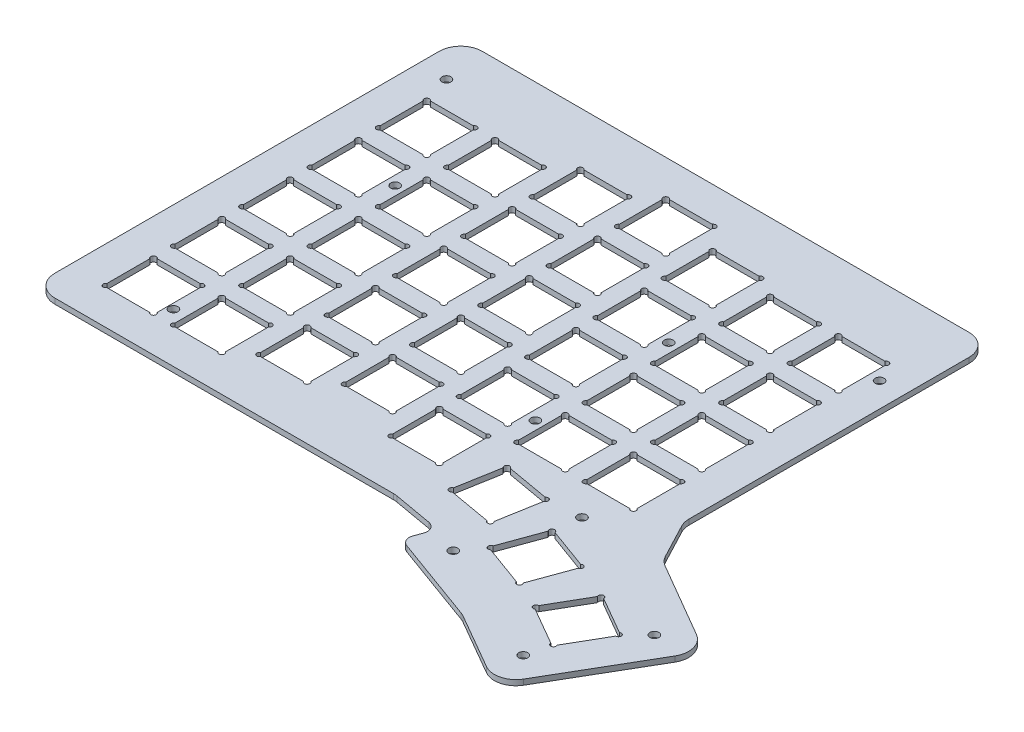
SolidWorks part; units mm, degrees
ref_plane "Front Plane" through (0, 0, 0) normal (0, 0, 1) x (1, 0, 0)
ref_plane "Top Plane" through (0, 0, 0) normal (0, 1, 0) x (1, 0, 0)
ref_plane "Right Plane" through (0, 0, 0) normal (1, 0, 0) x (0, 0, -1)
sketch "Sketch1" plane through (0, 0, 0) normal (0, 1, 0) x (1, 0, 0)
  line L0 (-117.355, 131.5231) -> (30.445, 131.523)
  line L3 (36.9567, 33.5861) -> (64.5736, 17.5122)
  line L4 (64.5736, 17.5122) -> (43.0375, -19.4893)
  line L5 (43.0375, -19.4893) -> (21.8815, -7.2748)
  line L6 (21.8815, -7.2748) -> (-4.8241, 2.4452)
  line L7 (-4.8241, 2.4452) -> (-2.1415, 9.8154)
  line L8 (-2.1415, 9.8154) -> (-16.3627, 12.323)
  line L9 (-16.3627, 12.323) -> (-117.355, 12.3231)
  line L10 (-117.355, 12.3231) -> (-117.355, 131.5231)
  line L12 (36.9567, 33.5861) -> (30.445, 45.9585)
  line L13 (30.445, 45.9585) -> (30.445, 131.523)
  line L22 (-114.355, 124.3231) -> (-114.355, 19.5231) construction
  line L24 (24.245, 128.523) -> (-110.155, 128.5231) construction
  line L26 (27.445, 40.923) -> (27.445, 125.323) construction
  line L27 (31.445, 33.323) -> (27.445, 40.923) construction
  line L30 (57.045, 18.423) -> (31.445, 33.323) construction
  line L31 (43.961, -12.1898) -> (58.3385, 12.7128) construction
  line L32 (23.0806, -4.503) -> (38.1322, -13.1931) construction
  line L33 (2.645, 2.923) -> (23.0806, -4.503) construction
  line L34 (-16.3823, 15.323) -> (0.7426, 12.3612) construction
  line L35 (1.4596, 10.95) -> (0.545, 8.423) construction
  dimension "D1" = 119.2
  dimension "D7" = 20
  dimension "D5" = 10
  dimension "D8" = 30
  dimension "D3" = 3
  dimension "D2" = 3
  dimension "D4" = 3
  dimension "D6" = 5
  dimension "D9" = 3
  dimension "D10" = 3
  dimension "D11" = 3
  dimension "D12" = 3
  dimension "D13" = 3
  dimension "D14" = 3
extrude "Boss-Extrude1" add sketch "Sketch1" against normal blind 1.5
sketch "Sketch2" plane through (0, 0, 0) normal (0, 1, 0) x (1, 0, 0)
  line L0 (-50.467, 121.823) -> (-36.467, 107.823) construction
  line L1 (-50.467, 121.823) -> (-36.467, 121.823)
  line L2 (-50.467, 121.823) -> (-50.467, 107.823)
  line L3 (-50.467, 107.823) -> (-36.467, 107.823)
  line L4 (-36.467, 121.823) -> (-36.467, 107.823)
  line L5 (-36.467, 121.823) -> (-50.467, 107.823) construction
  line L6 (30.445, 131.523) -> (-117.355, 131.5231) construction
  line L7 (-117.355, 131.5231) -> (-117.355, 12.3231) construction
  circle A0 centre (-50.1135, 121.4695) radius 0.75
  circle A1 centre (-36.8206, 121.4695) radius 0.75
  circle A2 centre (-36.8206, 108.1766) radius 0.75
  circle A3 centre (-50.1135, 108.1766) radius 0.75
  dimension "D5" = 1.5
  dimension "D1" = 14
  dimension "D3" = 9.7
  dimension "D2" = 66.888
  dimension "D4" = 0.5
extrude "Cut-Extrude1" cut sketch "Sketch2" against normal blind 10 contours L2 L3 L4 L1 | A0 | A3 | A2 | A1
sketch "Sketch3" plane through (0, 0, 0) normal (0, 1, 0) x (1, 0, 0)
  line L0 (-37.482, 121.823) -> (-49.452, 121.823) construction
  line L1 (-69.517, 117.0605) -> (-55.517, 117.0605)
  line L2 (-69.517, 117.0605) -> (-69.517, 103.0605)
  line L3 (-69.517, 103.0605) -> (-55.517, 103.0605)
  line L4 (-55.517, 117.0605) -> (-55.517, 103.0605)
  line L5 (-50.467, 114.823) -> (-36.467, 114.823) construction
  line L6 (-50.467, 120.8081) -> (-50.467, 108.838) construction
  line L7 (-36.467, 120.8081) -> (-36.467, 108.838) construction
  line L9 (-69.517, 117.0605) -> (-55.517, 103.0605) construction
  line L10 (-55.517, 117.0605) -> (-69.517, 103.0605) construction
  circle A0 centre (-69.1635, 116.707) radius 0.75
  circle A1 centre (-55.8706, 116.707) radius 0.75
  circle A2 centre (-55.8706, 103.4141) radius 0.75
  circle A3 centre (-69.1635, 103.4141) radius 0.75
  point P6 (-43.467, 121.823)
  point P7 (-62.517, 117.0605)
  dimension "D4" = 1.5
  dimension "D1" = 19.05
  dimension "D2" = 4.7625
  dimension "D3" = 0.5
sketch "Sketch4" plane through (0, 0, 0) normal (0, 1, 0) x (1, 0, 0)
  line L0 (-37.482, 121.823) -> (-49.452, 121.823) construction
  line L1 (-88.567, 112.298) -> (-74.567, 112.298)
  line L2 (-88.567, 112.298) -> (-88.567, 98.298)
  line L3 (-88.567, 98.298) -> (-74.567, 98.298)
  line L4 (-74.567, 112.298) -> (-74.567, 98.298)
  line L5 (-55.517, 117.0605) -> (-55.517, 103.0605) construction
  line L6 (-50.467, 114.823) -> (-36.467, 114.823) construction
  line L7 (-50.467, 120.8081) -> (-50.467, 108.838) construction
  line L8 (-36.467, 120.8081) -> (-36.467, 108.838) construction
  line L9 (-88.567, 112.298) -> (-74.567, 98.298) construction
  line L10 (-74.567, 112.298) -> (-88.567, 98.298) construction
  circle A0 centre (-88.2135, 111.9445) radius 0.75
  circle A1 centre (-74.9206, 111.9445) radius 0.75
  circle A2 centre (-74.9206, 98.6516) radius 0.75
  circle A3 centre (-88.2135, 98.6516) radius 0.75
  dimension "D4" = 0.5
  dimension "D3" = 1.5
  dimension "D1" = 9.525
  dimension "D2" = 19.05
sketch "Sketch5" plane through (0, 0, 0) normal (0, 1, 0) x (1, 0, 0)
  line L0 (-37.482, 121.823) -> (-49.452, 121.823) construction
  line L1 (-107.617, 112.298) -> (-93.617, 112.298)
  line L2 (-107.617, 112.298) -> (-107.617, 98.298)
  line L3 (-107.617, 98.298) -> (-93.617, 98.298)
  line L4 (-93.617, 112.298) -> (-93.617, 98.298)
  line L5 (-74.567, 112.298) -> (-74.567, 98.298) construction
  line L6 (-50.467, 114.823) -> (-36.467, 114.823) construction
  line L7 (-50.467, 120.8081) -> (-50.467, 108.838) construction
  line L8 (-36.467, 120.8081) -> (-36.467, 108.838) construction
  line L10 (-107.617, 112.298) -> (-93.617, 98.298) construction
  line L11 (-93.617, 112.298) -> (-107.617, 98.298) construction
  circle A0 centre (-107.2635, 111.9445) radius 0.75
  circle A1 centre (-93.9706, 111.9445) radius 0.75
  circle A2 centre (-93.9706, 98.6516) radius 0.75
  circle A3 centre (-107.2635, 98.6516) radius 0.75
  dimension "D4" = 1.5
  dimension "D1" = 19.05
  dimension "D3" = 0.5
  dimension "D2" = 9.525
sketch "Sketch6" plane through (0, 0, 0) normal (0, 1, 0) x (1, 0, 0)
  line L0 (-37.482, 121.823) -> (-49.452, 121.823) construction
  line L1 (-31.417, 115.823) -> (-17.417, 115.823)
  line L2 (-31.417, 115.823) -> (-31.417, 101.823)
  line L3 (-31.417, 101.823) -> (-17.417, 101.823)
  line L4 (-17.417, 115.823) -> (-17.417, 101.823)
  line L5 (-50.467, 120.8081) -> (-50.467, 108.838) construction
  line L6 (-31.417, 115.823) -> (-17.417, 101.823) construction
  line L7 (-17.417, 115.823) -> (-31.417, 101.823) construction
  line L8 (-50.467, 114.823) -> (-36.467, 114.823) construction
  line L9 (-50.467, 120.8081) -> (-50.467, 108.838) construction
  line L10 (-36.467, 120.8081) -> (-36.467, 108.838) construction
  circle A0 centre (-17.7706, 115.4695) radius 0.75
  circle A1 centre (-31.0635, 115.4695) radius 0.75
  circle A2 centre (-31.0635, 102.1766) radius 0.75
  circle A3 centre (-17.7706, 102.1766) radius 0.75
  dimension "D4" = 1.5
  dimension "D3" = 0.5
  dimension "D2" = 19.05
  dimension "D1" = 6
sketch "Sketch7" plane through (0, 0, 0) normal (0, 1, 0) x (1, 0, 0)
  line L0 (-37.482, 121.823) -> (-49.452, 121.823) construction
  line L1 (-12.367, 112.823) -> (1.633, 112.823)
  line L2 (-12.367, 112.823) -> (-12.367, 98.823)
  line L3 (-12.367, 98.823) -> (1.633, 98.823)
  line L4 (1.633, 112.823) -> (1.633, 98.823)
  line L5 (-31.417, 115.823) -> (-31.417, 101.823) construction
  line L6 (-12.367, 112.823) -> (1.633, 98.823) construction
  line L7 (1.633, 112.823) -> (-12.367, 98.823) construction
  line L8 (-36.467, 114.823) -> (-50.467, 114.823) construction
  line L9 (-36.467, 120.8081) -> (-36.467, 108.838) construction
  line L10 (-50.467, 120.8081) -> (-50.467, 108.838) construction
  circle A0 centre (-12.0135, 112.4695) radius 0.75
  circle A1 centre (1.2794, 112.4695) radius 0.75
  circle A2 centre (1.2794, 99.1766) radius 0.75
  circle A3 centre (-12.0135, 99.1766) radius 0.75
  dimension "D4" = 1.5
  dimension "D3" = 0.5
  dimension "D2" = 19.05
  dimension "D1" = 9
sketch "Sketch8" plane through (0, 0, 0) normal (0, 1, 0) x (1, 0, 0)
  line L0 (-37.482, 121.823) -> (-49.452, 121.823) construction
  line L1 (6.683, 112.823) -> (20.683, 112.823)
  line L2 (6.683, 112.823) -> (6.683, 98.823)
  line L3 (6.683, 98.823) -> (20.683, 98.823)
  line L4 (20.683, 112.823) -> (20.683, 98.823)
  line L5 (-12.367, 112.823) -> (-12.367, 98.823) construction
  line L6 (6.683, 112.823) -> (20.683, 98.823) construction
  line L7 (20.683, 112.823) -> (6.683, 98.823) construction
  line L8 (-50.467, 114.823) -> (-36.467, 114.823) construction
  line L9 (-50.467, 120.8081) -> (-50.467, 108.838) construction
  line L10 (-36.467, 120.8081) -> (-36.467, 108.838) construction
  circle A0 centre (7.0365, 112.4695) radius 0.75
  circle A1 centre (20.3294, 112.4695) radius 0.75
  circle A2 centre (20.3294, 99.1766) radius 0.75
  circle A3 centre (7.0365, 99.1766) radius 0.75
  dimension "D4" = 1.5
  dimension "D1" = 19.05
  dimension "D3" = 0.5
  dimension "D2" = 9
extrude "Cut-Extrude2" cut sketch "Sketch3" against normal blind 10 contours L1 L4 L3 L2 | A0 | A1 | A2 | A3
extrude "Cut-Extrude3" cut sketch "Sketch4" against normal blind 10 contours L1 L4 L3 L2 | A0 | A1 | A2 | A3
extrude "Cut-Extrude4" cut sketch "Sketch5" against normal blind 10 contours A0 | L1 L4 L3 L2 | A1 | A2 | A3
extrude "Cut-Extrude5" cut sketch "Sketch6" against normal blind 10 contours L1 L4 L3 L2 | A1 | A0 | A3 | A2
extrude "Cut-Extrude6" cut sketch "Sketch7" against normal blind 10 contours A0 | L1 L4 L3 L2 | A1 | A3 | A2
extrude "Cut-Extrude7" cut sketch "Sketch8" against normal blind 10 contours L1 L4 L3 L2 | A1 | A0 | A3 | A2
pattern_linear "LPattern1" count 5 spacing 19.05 along (0, 0, 1) of "Cut-Extrude5", "Cut-Extrude1", "Cut-Extrude2", "Cut-Extrude3", "Cut-Extrude4"
pattern_linear "LPattern2" count 4 spacing 19.05 along (0, 0, 1) of "Cut-Extrude7", "Cut-Extrude6"
sketch "Sketch10" plane through (0, 0, 0) normal (0, 1, 0) x (1, 0, 0)
  line L0 (-33.417, 41.623) -> (-15.417, 41.623) construction
  line L1 (-15.417, 41.623) -> (-15.417, 23.623) construction
  line L2 (-15.417, 23.623) -> (-33.417, 23.623) construction
  line L3 (-33.417, 23.623) -> (-33.417, 41.623) construction
  line L4 (-14.367, 57.673) -> (3.633, 57.673) construction
  line L5 (3.633, 57.673) -> (3.633, 39.673) construction
  line L6 (3.633, 39.673) -> (-14.367, 39.673) construction
  line L7 (-14.367, 39.673) -> (-14.367, 57.673) construction
  line L8 (-30.402, 39.623) -> (-18.432, 39.623) construction
  line L9 (-31.417, 38.6081) -> (-31.417, 26.638) construction
  line L10 (-11.352, 55.673) -> (0.618, 55.673) construction
  line L11 (-12.367, 54.6581) -> (-12.367, 42.688) construction
  line L12 (-7.669, 34.8561) -> (6.1183, 32.4251)
  line L13 (-7.669, 34.8561) -> (-10.1001, 21.0688)
  line L14 (6.1183, 32.4251) -> (3.6872, 18.6378)
  line L15 (-10.1001, 21.0688) -> (3.6872, 18.6378)
  line L16 (-7.669, 34.8561) -> (3.6872, 18.6378) construction
  line L17 (6.1183, 32.4251) -> (-10.1001, 21.0688) construction
  line L18 (-50.467, 114.823) -> (-36.467, 114.823) construction
  line L19 (-50.467, 120.8081) -> (-50.467, 108.838) construction
  line L21 (-30.402, 25.623) -> (-18.432, 25.623) construction
  line L22 (-36.467, 120.8081) -> (-36.467, 108.838) construction
  line L23 (-12.417, 19.4465) -> (-9.2914, 37.173) construction
  line L24 (-9.2914, 37.173) -> (8.4352, 34.0474) construction
  line L25 (8.4352, 34.0474) -> (5.3095, 16.3208) construction
  line L26 (5.3095, 16.3208) -> (-12.417, 19.4465) construction
  line L27 (-8.8846, 27.9625) -> (-10.8542, 28.3098) construction
  line L28 (-0.7754, 33.6406) -> (-0.4281, 35.6102) construction
  circle A0 centre (-7.3823, 34.4466) radius 0.75
  circle A1 centre (5.7087, 32.1383) radius 0.75
  circle A2 centre (3.4004, 19.0473) radius 0.75
  circle A3 centre (-9.6905, 21.3556) radius 0.75
  point P10 (-24.417, 39.623)
  point P11 (-24.417, 41.623)
  point P14 (-31.417, 32.623)
  point P15 (-33.417, 32.623)
  point P18 (-5.367, 55.673)
  point P19 (-5.367, 57.673)
  point P22 (-12.367, 48.673)
  point P23 (-14.367, 48.673)
  dimension "D11" = 1.5
  dimension "D1" = 18
  dimension "D2" = 10
  dimension "D3" = 90
  dimension "D4" = 90
  dimension "D5" = 3
  dimension "D6" = 2.5
  dimension "D7" = 0.5
  dimension "D8" = 0.5
  dimension "D9" = 0.5
  dimension "D10" = 0.5
extrude "Cut-Extrude8" cut sketch "Sketch10" against normal blind 10 contours L12 L14 L15 L13 | A0 | A1 | A2 | A3
sketch "Sketch11" plane through (0, 0, 0) normal (0, 1, 0) x (1, 0, 0)
  line L4 (14.4184, 32.5759) -> (31.3328, 26.4195) construction
  line L5 (14.4184, 32.5759) -> (5.1838, 7.2042) construction
  line L6 (31.3328, 26.4195) -> (22.0983, 1.0478) construction
  line L7 (5.1838, 7.2042) -> (22.0983, 1.0478) construction
  line L8 (14.0746, 25.7838) -> (22.4421, 7.8398) construction
  line L9 (27.2303, 20.9955) -> (9.2864, 12.6281) construction
  line L10 (-9.2914, 37.173) -> (8.4352, 34.0474) construction
  line L11 (8.4352, 34.0474) -> (5.3095, 16.3208) construction
  line L12 (5.3095, 16.3208) -> (-12.417, 19.4465) construction
  line L13 (-12.417, 19.4465) -> (-9.2914, 37.173) construction
  line L14 (-6.6695, 34.6799) -> (5.1187, 32.6013) construction
  line L15 (-7.8453, 33.8566) -> (-9.9239, 22.0684) construction
  line L16 (-0.7754, 33.6406) -> (-0.4281, 35.6102) construction
  line L17 (-8.8846, 27.9625) -> (-10.8542, 28.3098) construction
  line L18 (-50.467, 114.823) -> (-36.467, 114.823) construction
  line L19 (-50.467, 120.8081) -> (-50.467, 108.838) construction
  line L20 (14.0746, 25.7838) -> (27.2303, 20.9955)
  line L21 (27.2303, 20.9955) -> (22.4421, 7.8398)
  line L22 (22.4421, 7.8398) -> (9.2864, 12.6281)
  line L23 (9.2864, 12.6281) -> (14.0746, 25.7838)
  line L24 (-30.402, 25.623) -> (-18.432, 25.623) construction
  line L25 (11.6805, 19.206) -> (9.8011, 19.89) construction
  line L26 (20.6525, 23.3897) -> (22.8756, 29.4977) construction
  line L32 (-36.467, 120.8081) -> (-36.467, 108.838) construction
  line L39 (5.1838, 7.2042) -> (22.0983, 1.0478) construction
  circle A0 centre (14.2859, 25.3307) radius 0.75
  circle A1 centre (26.7772, 20.7842) radius 0.75
  circle A2 centre (22.2307, 8.293) radius 0.75
  circle A3 centre (9.7395, 12.8394) radius 0.75
  dimension "D9" = 3
  dimension "D1" = 18
  dimension "D4" = 90
  dimension "D15" = 1.5
  dimension "D2" = 90
  dimension "D3" = 90
  dimension "D5" = 20
  dimension "D6" = 90
  dimension "D7" = 90
  dimension "D8" = 27
  dimension "D10" = 27
  dimension "D11" = 0.5
  dimension "D12" = 0.5
  dimension "D13" = 0.5
  dimension "D14" = 0.5
sketch "Sketch12" plane through (0, 0, 0) normal (0, 1, 0) x (1, 0, 0)
  line L0 (36.8994, 16.7752) -> (49.0238, 9.7752)
  line L1 (49.0238, 9.7752) -> (42.0238, -2.3491)
  line L2 (42.0238, -2.3491) -> (29.8994, 4.6509)
  line L3 (29.8994, 4.6509) -> (36.8994, 16.7752)
  line L5 (-50.467, 114.823) -> (-36.467, 114.823) construction
  line L6 (-117.355, 12.3231) -> (-16.3627, 12.323) construction
  line L7 (5.1838, 7.2042) -> (22.0983, 1.0478) construction
  line L8 (22.0983, 1.0478) -> (103.4201, -28.5509) construction
  line L9 (24.9174, 0.0217) -> (38.4174, 23.4044)
  line L10 (38.4174, 23.4044) -> (54.0059, 14.4044)
  line L11 (54.0059, 14.4044) -> (40.5058, -8.9783)
  line L12 (40.5058, -8.9783) -> (24.9174, 0.0217)
  line L13 (42.9616, 13.2752) -> (46.2116, 18.9044) construction
  line L14 (33.3994, 10.7131) -> (31.6674, 11.7131) construction
  line L15 (31.3328, 26.4195) -> (22.0983, 1.0478) construction
  line L16 (14.4184, 32.5759) -> (31.3328, 26.4195) construction
  line L17 (-50.467, 120.8081) -> (-50.467, 108.838) construction
  line L18 (-36.467, 120.8081) -> (-36.467, 108.838) construction
  line L19 (36.8994, 16.7752) -> (42.0238, -2.3491) construction
  line L20 (29.8994, 4.6509) -> (49.0238, 9.7752) construction
  circle A0 centre (37.0289, 16.2923) radius 0.75
  circle A1 centre (48.5408, 9.6458) radius 0.75
  circle A2 centre (41.8944, -1.8661) radius 0.75
  circle A3 centre (30.3824, 4.7803) radius 0.75
  dimension "D4" = 3
  dimension "D5" = 1.5
  dimension "D3" = 90
  dimension "D7" = 0.5
  dimension "D8" = 0.5
  dimension "D9" = 0.5
  dimension "D1" = 30
  dimension "D2" = 90
  dimension "D6" = 0.5
extrude "Cut-Extrude10" cut sketch "Sketch11" against normal blind 10 contours L20 L21 L22 L23 | A0 | A1 | A3 | A2
extrude "Cut-Extrude11" cut sketch "Sketch12" against normal blind 10 contours L0 L1 L2 L3 | A0 | A3 | A2 | A1
sketch "Sketch50" plane through (0, 0, 0) normal (0, -1, 0) x (-1, 0, 0)
  circle A1 centre (109.5695, 119.7531) radius 1.25
  circle A2 centre (-23.6305, 107.353) radius 1.25
  circle A4 centre (92.1245, 26.1671) radius 1.25
  circle A6 centre (14.9695, 87.153) radius 1.25
  circle A8 centre (-15.1305, 32.853) radius 1.25
  circle A10 centre (-53.6304, 14.553) radius 1.25
  circle A12 centre (-40.2304, -8.647) radius 1.25
  circle A14 centre (-5.2304, 6.853) radius 1.25
  circle A16 centre (14.7695, 49.753) radius 1.25
  circle A18 centre (91.0695, 86.9531) radius 1.25
  dimension "D2" = 2.5
  dimension "D3" = 2.5
  dimension "D5" = 2.5
  dimension "D7" = 2.5
  dimension "D9" = 2.5
  dimension "D11" = 2.5
  dimension "D13" = 2.5
  dimension "D15" = 2.5
  dimension "D17" = 2.5
  dimension "D19" = 2.5
extrude "Cut-Extrude13" cut sketch "Sketch50" along normal blind 10
fillet "Fillet1" radius 6 9 edges at (-117.355, -0.75, -131.5231) (-117.355, -0.75, -12.3231) (-16.3627, -0.75, -12.323) (21.8815, -0.75, 7.2748) (43.0375, -0.75, 19.4893) (64.5736, -0.75, -17.5122) (36.9567, -0.75, -33.5861) (30.445, -0.75, -45.9585) (30.445, -0.75, -131.523)
fillet "Fillet2" radius 2.5 2 edges at (-2.1415, -0.75, -9.8154) (-4.8241, -0.75, -2.4452)
equation "\"EDGE_PAD\"=3"
equation "\"D1@Sketch1\"=\"EDGE_PAD\"*2+113.2"
equation "\"LAYER_SWITCH_THICKNESS\"= 1.5"
equation "\"D1@Boss-Extrude1\"=\"LAYER_SWITCH_THICKNESS\""
equation "\"CUTOUT_SIZE\"= 14"
equation "\"D1@Sketch2\"=\"CUTOUT_SIZE\""
equation "\"D2@Sketch2\"=\"EDGE_PAD\"+63.888"
equation "\"D3@Sketch2\"=\"EDGE_PAD\"+6.7"
equation "\"CASE_THICKNESS\"= 3"
equation "\"SCREW_SIZE\"= 2.5"
equation "\"D2@Sketch50\"=\"SCREW_SIZE\""
equation "\"OUTER_SCREW_SIZE\"= 4"
equation "\"D3@Sketch50\"=\"SCREW_SIZE\""
equation "\"D5@Sketch50\"=\"SCREW_SIZE\""
equation "\"D7@Sketch50\"=\"SCREW_SIZE\""
equation "\"D9@Sketch50\"=\"SCREW_SIZE\""
equation "\"D11@Sketch50\"=\"SCREW_SIZE\""
equation "\"D13@Sketch50\"=\"SCREW_SIZE\""
equation "\"D15@Sketch50\"=\"SCREW_SIZE\""
equation "\"D17@Sketch50\"=\"SCREW_SIZE\""
equation "\"D3@Sketch1\"=\"EDGE_PAD\""
equation "\"D2@Sketch1\"=\"EDGE_PAD\""
equation "\"D4@Sketch1\"=\"EDGE_PAD\""
equation "\"D6@Sketch1\"=\"EDGE_PAD\"+2"
equation "\"D9@Sketch1\"=\"EDGE_PAD\""
equation "\"D10@Sketch1\"=\"EDGE_PAD\""
equation "\"D11@Sketch1\"=\"EDGE_PAD\""
equation "\"D12@Sketch1\"=\"EDGE_PAD\""
equation "\"D13@Sketch1\"=\"EDGE_PAD\""
equation "\"D14@Sketch1\"=\"EDGE_PAD\""
equation "\"D19@Sketch50\"=\"SCREW_SIZE\""
equation "\"EDGE_CIRCLES\"= 1.5"
equation "\"EDGE_CIRCLES_OFFSET\"= 0.5"
equation "\"D5@Sketch2\"=\"EDGE_CIRCLES\""
equation "\"D4@Sketch2\"=\"EDGE_CIRCLES_OFFSET\""
equation "\"D3@Sketch3\"=\"EDGE_CIRCLES_OFFSET\""
equation "\"D4@Sketch3\"=\"EDGE_CIRCLES\""
equation "\"D3@Sketch4\"=\"EDGE_CIRCLES\""
equation "\"D4@Sketch4\"=\"EDGE_CIRCLES_OFFSET\""
equation "\"D3@Sketch5\"=\"EDGE_CIRCLES_OFFSET\""
equation "\"D4@Sketch5\"=\"EDGE_CIRCLES\""
equation "\"D3@Sketch6\"=\"EDGE_CIRCLES_OFFSET\""
equation "\"D4@Sketch6\"=\"EDGE_CIRCLES\""
equation "\"D3@Sketch7\"=\"EDGE_CIRCLES_OFFSET\""
equation "\"D4@Sketch7\"=\"EDGE_CIRCLES\""
equation "\"D3@Sketch8\"=\"EDGE_CIRCLES_OFFSET\""
equation "\"D4@Sketch8\"=\"EDGE_CIRCLES\""
equation "\"D7@Sketch10\"=\"EDGE_CIRCLES_OFFSET\""
equation "\"D8@Sketch10\"=\"EDGE_CIRCLES_OFFSET\""
equation "\"D9@Sketch10\"=\"EDGE_CIRCLES_OFFSET\""
equation "\"D10@Sketch10\"=\"EDGE_CIRCLES_OFFSET\""
equation "\"D11@Sketch10\"=\"EDGE_CIRCLES\""
equation "\"D11@Sketch11\"=\"EDGE_CIRCLES_OFFSET\""
equation "\"D12@Sketch11\"=\"EDGE_CIRCLES_OFFSET\""
equation "\"D13@Sketch11\"=\"EDGE_CIRCLES_OFFSET\""
equation "\"D14@Sketch11\"=\"EDGE_CIRCLES_OFFSET\""
equation "\"D15@Sketch11\"=\"EDGE_CIRCLES\""
equation "\"D5@Sketch12\"=\"EDGE_CIRCLES\""
equation "\"D6@Sketch12\"=\"EDGE_CIRCLES_OFFSET\""
equation "\"D7@Sketch12\"=\"EDGE_CIRCLES_OFFSET\""
equation "\"D8@Sketch12\"=\"EDGE_CIRCLES_OFFSET\""
equation "\"D9@Sketch12\"=\"EDGE_CIRCLES_OFFSET\""
